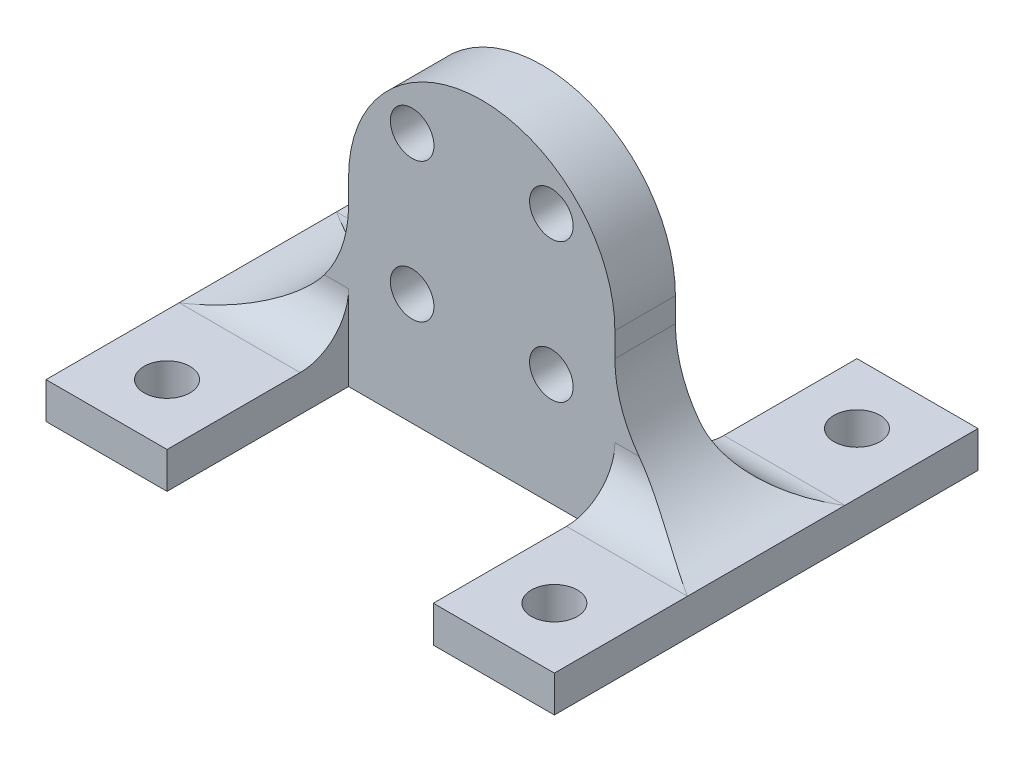
SolidWorks part; units mm, degrees
ref_plane "Front Plane" through (0, 0, 0) normal (0, 0, 1) x (1, 0, 0)
ref_plane "Top Plane" through (0, 0, 0) normal (0, 1, 0) x (1, 0, 0)
ref_plane "Right Plane" through (0, 0, 0) normal (1, 0, 0) x (0, 0, -1)
sketch "Sketch1" plane through (0, 0, 0) normal (0, 0, 1) x (1, 0, 0)
  line L1 (-5.75, 5.75) -> (5.75, 5.75) construction
  line L2 (-5.75, 5.75) -> (-5.75, -5.75) construction
  line L3 (-5.75, -5.75) -> (5.75, -5.75) construction
  line L4 (5.75, 5.75) -> (5.75, -5.75) construction
  line L5 (-5.75, 5.75) -> (5.75, -5.75) construction
  line L6 (-5.75, -5.75) -> (5.75, 5.75) construction
  circle A0 centre (-5.75, 5.75) radius 1.8
  circle A1 centre (5.75, 5.75) radius 1.8
  circle A2 centre (5.75, -5.75) radius 1.8
  circle A3 centre (-5.75, -5.75) radius 1.8
  circle A4 centre (0, 0) radius 11
  point P0 (0, 0)
  dimension "D1" = 3.6
  dimension "D3" = 22
  dimension "D2" = 11.5
extrude "Boss-Extrude1" add sketch "Sketch1" along normal blind 5
sketch "Sketch2" plane through (0, 0, 0) normal (0, 0, -1) x (-1, 0, 0)
  line L0 (-11, 0) -> (-11, -12)
  line L1 (-11, -12) -> (11, -12)
  line L2 (11, -12) -> (11, 0)
  arc A0 (-11, 0) -> (11, 0) centre (0, 0) ccw
  circle A1 centre (0, 0) radius 11 construction
  point P6 (0, -11)
  circle M1 centre (0, 0) radius 11
  dimension "D1" = 1
extrude "Boss-Extrude2" add sketch "Sketch2" against normal up to surface (5 mm away) contours L0 L1 M1 | L1 L2 M1 region at (0, -11.2506, 0) up to face at (7.55, -5.75, 5)
sketch "Sketch3" plane through (0, -12, 0) normal (0, -1, 0) x (1, 0, 0)
  line L0 (0, 0) -> (0, 5) construction
  line L1 (11, 5) -> (-11, 5) construction
  line L7 (11, 5) -> (11, 0) construction
  line L8 (-11, 5) -> (-11, 0) construction
  line L9 (-11, 5) -> (-11, 20)
  line L10 (-11, 20) -> (-21, 20)
  line L11 (-21, 20) -> (-21, -15)
  line L12 (-21, -15) -> (-11, -15)
  line L13 (-11, -15) -> (-11, 0)
  line L14 (-11, 0) -> (11, 0)
  line L15 (11, 0) -> (11, -15)
  line L16 (11, -15) -> (21, -15)
  line L17 (21, -15) -> (21, 20)
  line L18 (21, 20) -> (11, 20)
  line L19 (11, 20) -> (11, 5)
  line L21 (11, 5) -> (-11, 5)
  line L22 (0, 2.5) -> (6.1746, 2.5) construction
  line L23 (16, -15) -> (16, -10) construction
  circle A4 centre (16, -10) radius 1.9
  circle A5 centre (16, 15) radius 1.9
  circle A6 centre (-16, 15) radius 1.9
  circle A7 centre (-16, -10) radius 1.9
  point P5 (0, 2.5)
  dimension "D4" = 5
  dimension "D5" = 3.8
  dimension "D2" = 10
  dimension "D3" = 15
extrude "Boss-Extrude3" add sketch "Sketch3" along normal blind 3
fillet "Fillet2" radius 10 2 edges at (11, -12, 2.5) (-11, -12, 2.5)
fillet "Fillet3" radius 4 4 edges at (16, -12, 0) (16, -12, 5) (-16, -12, 5) (-16, -12, 0)
